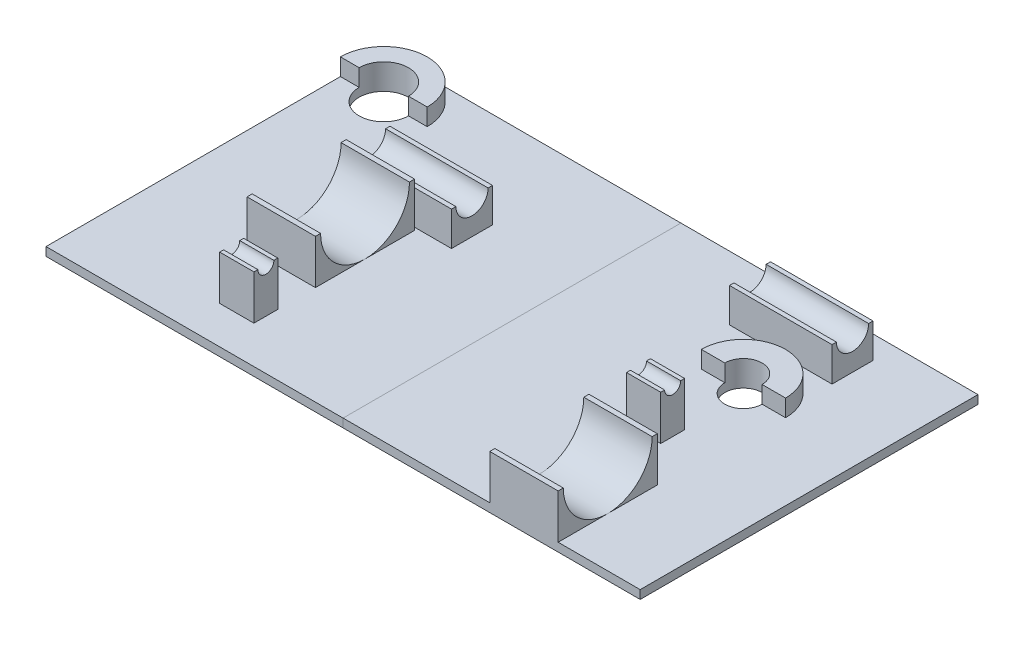
SolidWorks part; units mm, degrees
ref_plane "Front Plane" through (0, 0, 0) normal (0, 0, 1) x (1, 0, 0)
ref_plane "Top Plane" through (0, 0, 0) normal (0, 1, 0) x (1, 0, 0)
ref_plane "Right Plane" through (0, 0, 0) normal (1, 0, 0) x (0, 0, -1)
sketch "Sketch1" plane through (0, 0, 0) normal (0, 1, 0) x (1, 0, 0)
  line L0 (-110.3757, 125.5014) -> (110.3757, 125.5014)
  line L1 (110.3757, 125.5014) -> (110.3757, 0)
  line L2 (110.3757, 0) -> (-110.3757, 0)
  line L3 (-110.3757, 0) -> (-110.3757, 125.5014)
  line L12 (-59.8043, 13.97) -> (-47.1043, 13.97)
  line L13 (-47.1043, 13.97) -> (-47.1043, 22.86)
  line L14 (-47.1043, 22.86) -> (-59.8043, 22.86)
  line L15 (-59.8043, 22.86) -> (-59.8043, 13.97)
  line L16 (79.8957, 36.83) -> (79.8957, 0)
  line L17 (79.8957, 0) -> (54.4957, 0)
  line L18 (54.4957, 0) -> (54.4957, 36.83)
  line L19 (54.4957, 36.83) -> (79.8957, 36.83)
  line L28 (0, 125.5014) -> (0, 0) construction
  line L29 (-110.3757, 62.7507) -> (110.3757, 62.7507) construction
  line L38 (67.1957, 59.69) -> (67.1957, 50.8)
  line L39 (67.1957, 50.8) -> (54.4957, 50.8)
  line L40 (54.4957, 50.8) -> (54.4957, 59.69)
  line L41 (54.4957, 59.69) -> (67.1957, 59.69)
  line L42 (-47.1043, 73.66) -> (-72.5043, 73.66)
  line L43 (-47.1043, 36.83) -> (-47.1043, 73.66)
  line L44 (-72.5043, 73.66) -> (-72.5043, 36.83)
  line L45 (-72.5043, 36.83) -> (-47.1043, 36.83)
  line L46 (-110.3757, 109.3724) -> (-103.4066, 109.3724)
  line L47 (-78.1177, 109.3724) -> (-85.0868, 109.3724)
  line L48 (-94.2467, 118.5323) -> (-103.4066, 109.3724) construction
  line L49 (-103.4066, 109.3724) -> (-94.2467, 100.2125) construction
  line L50 (-94.2467, 100.2125) -> (-85.0868, 109.3724) construction
  line L51 (-85.0868, 109.3724) -> (-94.2467, 118.5323) construction
  line L52 (66.4464, 89.2108) -> (59.5316, 82.296) construction
  line L53 (59.5316, 82.296) -> (66.4464, 75.3812) construction
  line L54 (66.4464, 75.3812) -> (73.3612, 82.296) construction
  line L55 (73.3612, 82.296) -> (66.4464, 89.2108) construction
  line L56 (-72.5043, 89.916) -> (-72.5043, 74.676)
  line L57 (-72.5043, 74.676) -> (-34.4043, 74.676)
  line L58 (-34.4043, 74.676) -> (-34.4043, 89.916)
  line L59 (-34.4043, 89.916) -> (-72.5043, 89.916)
  line L60 (41.7957, 116.9924) -> (79.8957, 116.9924)
  line L61 (79.8957, 116.9924) -> (79.8957, 101.7524)
  line L62 (79.8957, 101.7524) -> (41.7957, 101.7524)
  line L63 (41.7957, 101.7524) -> (41.7957, 116.9924)
  line L64 (73.3612, 82.296) -> (82.0928, 82.296)
  line L65 (50.8, 82.296) -> (59.5316, 82.296)
  arc A0 (-110.3757, 109.3724) -> (-78.1177, 109.3724) centre (-94.2467, 109.3724) cw
  circle A1 centre (-94.2467, 109.3724) radius 9.1599
  circle A2 centre (66.4464, 82.296) radius 6.9148
  arc A3 (50.8, 82.296) -> (82.0928, 82.296) centre (66.4464, 82.296) cw
  point P13 (-47.1043, 18.415)
  point P14 (54.4957, 18.415)
  point P18 (-47.1043, 55.245)
  point P19 (54.4957, 55.245)
  point P21 (70.3996, 78.9236)
  point P53 (41.7957, 109.3724)
  point P55 (83.7909, 79.352)
  point P56 (-34.4043, 82.296)
  point P57 (0, 0)
  point P58 (66.4464, 78.8728)
  point P59 (-94.2467, 105.6641)
  point P60 (-94.2467, 125.5014)
  point P61 (66.4464, 97.9424)
  point P62 (-59.8043, 36.83)
  point P63 (67.1957, 36.83)
  dimension "D9" = 32.258
  dimension "D10" = 12.954
  dimension "D12" = 31.2928
  dimension "D1" = 220.7514
  dimension "D2" = 125.5014
  dimension "D3" = 36.83
  dimension "D4" = 8.89
  dimension "D5" = 114.3
  dimension "D7" = 25.4
  dimension "D8" = 30.48
  dimension "D6" = 12.7
  dimension "D11" = 9.779
  dimension "D13" = 15.24
  dimension "D14" = 3.81
  dimension "D15" = 38.1
  dimension "D16" = 50.8
extrude "Base" add sketch "Sketch1" along normal blind 3.175 contours A2 | A1 | L2 L3 L0 L1 region at (-94.2467, 0, -109.3724) region at (66.4464, 0, -82.296)
extrude "Ratchet Handle" add sketch "Sketch1<3>" along normal blind 15.875 contours L59 L56 L57 L58 | L60 L61 L62 L63
sketch "Sketch1<3>" plane through (0, 0, 0) normal (0, 1, 0) x (1, 0, 0) same geometry as "Sketch1"
extrude "Ratchet Head" add sketch "Sketch1<4>" along normal blind 9.525 contours A1 L47 A0 L46 | A3 L65 A2 L64 region at (-83.0968, 0, -120.5223) region at (66.4464, 0, -89.836)
sketch "Sketch1<4>" plane through (0, 0, 0) normal (0, 1, 0) x (1, 0, 0) same geometry as "Sketch1"
extrude "Screwdriver" add sketch "Sketch1<5>" along normal blind 19.685 contours L14 L15 L12 L13 | L44 L45 L43 L42 | L41 L40 L39 L38 | L19 L18 L2 L16 region at (67.1957, 0, -18.415) region at (-53.4543, 0, -18.415) region at (60.8457, 0, -55.245) region at (-59.8043, 0, -55.245)
sketch "Sketch1<5>" plane through (0, 0, 0) normal (0, 1, 0) x (1, 0, 0) same geometry as "Sketch1"
sketch "Sketch2" plane through (0, 0, 0) normal (1, 0, 0) x (0, 0, -1)
  line L0 (22.86, 19.685) -> (13.97, 19.685) construction
  line L1 (73.66, 19.685) -> (36.83, 19.685) construction
  line L2 (101.7524, 15.875) -> (116.9924, 15.875) construction
  line L3 (89.916, 15.875) -> (74.676, 15.875) construction
  circle A0 centre (18.415, 19.685) radius 2.9845
  circle A1 centre (18.415, 19.685) radius 16.51
  circle A2 centre (55.245, 19.685) radius 2.9845
  circle A3 centre (55.245, 19.685) radius 16.51
  circle A4 centre (109.3724, 15.875) radius 5.9817
  circle A5 centre (82.296, 15.875) radius 5.9817
  dimension "D1" = 5.969
  dimension "D2" = 33.02
  dimension "D3" = 11.9634
extrude "Screwdriver Left Cut" cut sketch "Sketch2" against normal through all contours A3 A2 | A0 | A2 region at (0, 19.685, -18.415) region at (0, 19.685, -55.245) region at (0, 19.685, -39.202)
extrude "Screwdriver Right Cut" cut sketch "Sketch2<3>" along normal through all contours A1 A0 | A0 | A2 region at (0, 19.685, -18.415) region at (0, 19.685, -2.372) region at (0, 19.685, -55.245)
sketch "Sketch2<3>" plane through (0, 0, 0) normal (1, 0, 0) x (0, 0, -1) same geometry as "Sketch2"
extrude "Front Ratchet Cut" cut sketch "Sketch2<4>" against normal through all contours A5 region at (0, 15.875, -82.296)
sketch "Sketch2<4>" plane through (0, 0, 0) normal (1, 0, 0) x (0, 0, -1) same geometry as "Sketch2"
extrude "Back Ratchet Cut" cut sketch "Sketch2<5>" along normal through all contours A4 region at (0, 15.875, -109.3724)
sketch "Sketch2<5>" plane through (0, 0, 0) normal (1, 0, 0) x (0, 0, -1) same geometry as "Sketch2"
sketch "Sketch4" plane through (0, 0, 0) normal (0, 0, 1) x (1, 0, 0)
  line L0 (0, 0) -> (0, 3.175)
  line L1 (54.4957, 3.175) -> (-110.3757, 3.175) construction
split "Split2" trim tools "Sketch4" bodies to split 109 resulting bodies 122 123
